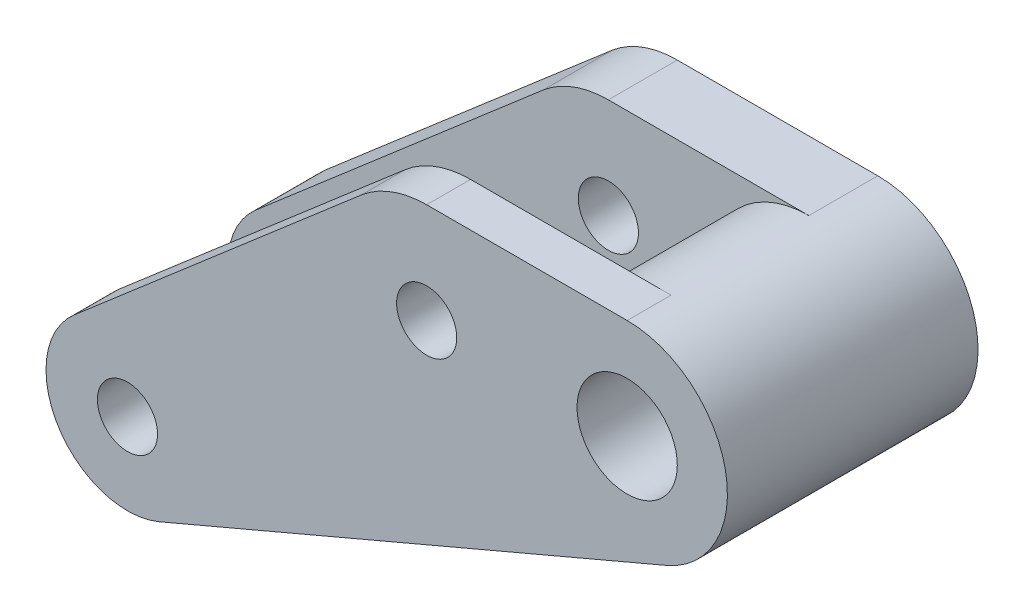
SolidWorks part; units mm, degrees
ref_plane "Front Plane" through (0, 0, 0) normal (0, 0, 1) x (1, 0, 0)
ref_plane "Top Plane" through (0, 0, 0) normal (0, 1, 0) x (1, 0, 0)
ref_plane "Right Plane" through (0, 0, 0) normal (1, 0, 0) x (0, 0, -1)
sketch "Sketch1" plane through (0, 0, 0) normal (0, 0, 1) x (1, 0, 0)
  line L0 (-12.7, 0) -> (0, 0) construction
  line L3 (-31.6528, -14.7599) -> (0, 0) construction
  line L6 (-29.633, -19.5075) -> (2.4859, -5.8432)
  line L7 (0, 0) -> (-31.6528, -14.7599) construction
  line L8 (-35.0207, -10.8515) -> (-16.8451, 4.8104)
  line L9 (-12.7, 6.35) -> (0, 6.35)
  arc A0 (2.4859, -5.8432) -> (0, 6.35) centre (0, 0) ccw
  arc A3 (-35.0207, -10.8515) -> (-29.633, -19.5075) centre (-31.6528, -14.7599) ccw
  circle A4 centre (-12.7, 0) radius 1.905
  circle A5 centre (-31.6528, -14.7599) radius 1.905
  circle A6 centre (0, 0) radius 3.175
  arc A8 (-12.7, 6.35) -> (-16.8451, 4.8104) centre (-12.7, 0) ccw
  dimension "D3" = 3.81
  dimension "D4" = 10.3187
  dimension "D5" = 6.35
  dimension "D6" = 6.35
  dimension "D8" = 3.81
  dimension "D9" = 6.35
  dimension "D1" = 12.7
  dimension "D2" = 34.925
  dimension "D7" = 25
extrude "Boss-Extrude1" add sketch "Sketch1" against normal blind 15.875
sketch "Sketch5" plane through (0, 0, 0) normal (0, 0, 1) x (1, 0, 0)
  line L0 (-16.8451, 4.8104) -> (-35.0207, -10.8515) construction
  line L1 (-29.633, -19.5075) -> (2.4859, -5.8432) construction
  line L2 (-26.4934, -3.5035) -> (-35.0207, -10.8515)
  line L3 (-29.633, -19.5075) -> (-26.4934, -18.1719)
  line L4 (-26.4934, -18.1719) -> (-26.4934, -3.5035)
  arc A0 (-35.0207, -10.8515) -> (-29.633, -19.5075) centre (-31.6528, -14.7599) ccw construction
  arc A1 (-35.0207, -10.8515) -> (-29.633, -19.5075) centre (-31.6528, -14.7599) ccw
  circle A2 centre (-31.6528, -14.7599) radius 5.1594 construction
extrude "Cut-Extrude3" [suppressed] cut sketch "Sketch5" against normal blind 9.525
ref_plane "Plane1" through (0, 0, -7.1437) normal (0, 0, 1) x (1, 0, 0)
sketch "Sketch4" plane through (0, 0, -7.1437) normal (0, 0, 1) x (1, 0, 0)
  line L7 (0, 6.35) -> (-12.7, 6.35) construction
  line L8 (-16.8451, 4.8104) -> (-35.0207, -10.8515) construction
  line L10 (0, 6.35) -> (-12.7, 6.35)
  line L11 (-16.8451, 4.8104) -> (-35.0207, -10.8515)
  line L12 (-15.074, -5.8895) -> (-20.2858, -3.7888)
  line L14 (-27.0539, -17.0985) -> (-20.2858, -3.7888)
  line L15 (-29.633, -19.5075) -> (2.4859, -5.8432) construction
  arc A8 (-35.0207, -10.8515) -> (-29.633, -19.5075) centre (-31.6528, -14.7599) ccw construction
  arc A12 (-35.0207, -10.8515) -> (-29.633, -19.5075) centre (-31.6528, -14.7599) ccw
  arc A13 (0, 6.35) -> (-6.35, 0) centre (0, 0) ccw
  arc A16 (-15.074, -5.8895) -> (-6.35, 0) centre (-12.7, 0) ccw
  arc A17 (-12.7, 6.35) -> (-16.8451, 4.8104) centre (-12.7, 0) ccw construction
  arc A18 (-12.7, 6.35) -> (-16.8451, 4.8104) centre (-12.7, 0) ccw
  arc A19 (-29.633, -19.5075) -> (-27.0539, -17.0985) centre (-31.6528, -14.7599) ccw
  point P1 (-17.4878, -5.5784)
  point P15 (-17.257, -5.1597)
  point P17 (-22.1171, -9.7051)
  point P18 (-19.2497, -7.172)
  point P19 (-17.3068, -5.7238)
  dimension "D1" = 6.35
  dimension "D2" = 40
  dimension "D3" = 95
extrude "Cut-Extrude2" cut sketch "Sketch4" against normal mid plane 8.7312
